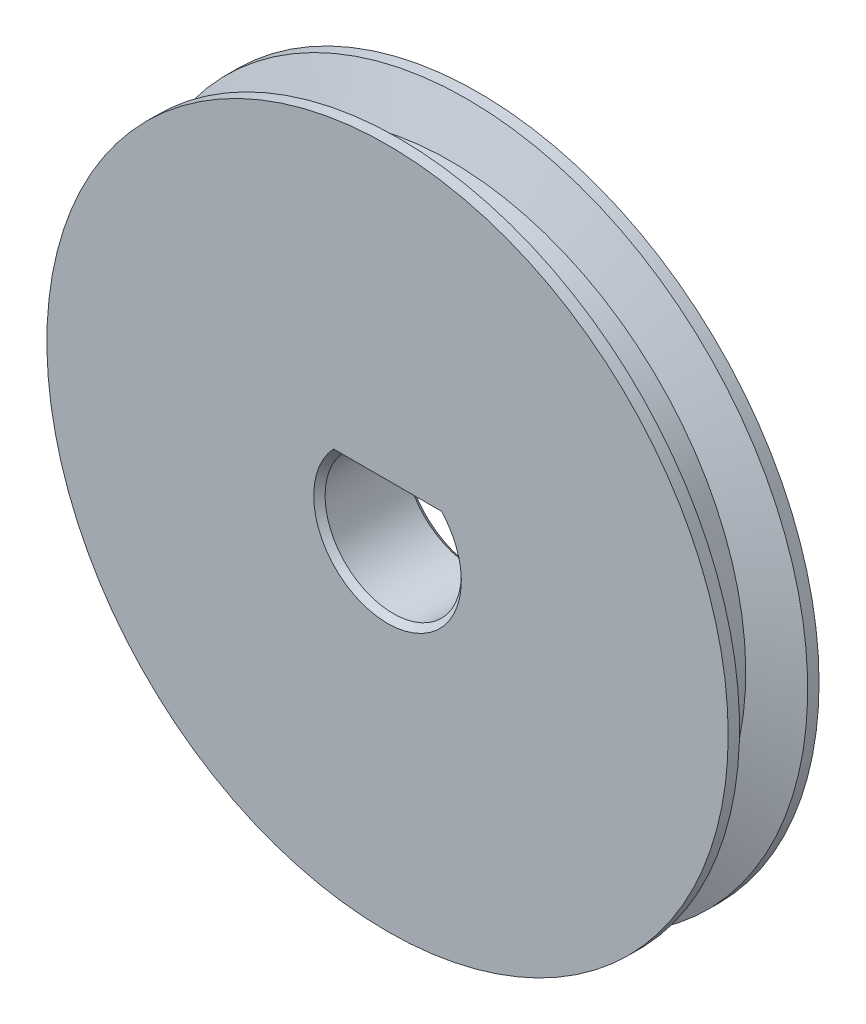
SolidWorks part; units mm, degrees
material "6061-T6 (SS)"
ref_plane "Front Plane" through (0, 0, 0) normal (0, 0, 1) x (1, 0, 0)
ref_plane "Top Plane" through (0, 0, 0) normal (0, 1, 0) x (1, 0, 0)
ref_plane "Right Plane" through (0, 0, 0) normal (1, 0, 0) x (0, 0, -1)
sketch "Sketch1" plane through (0, 0, 0) normal (0, 0, 1) x (1, 0, 0)
  circle A0 centre (0, 0) radius 47.625
  circle A1 centre (0, 0) radius 9.525
  dimension "D1" = 95.25
  dimension "D2" = 19.05
extrude "Extrude1" add sketch "Sketch1" along normal mid plane 12.7
sketch "Sketch2" plane through (0, 0, 0) normal (1, 0, 0) x (0, 0, -1)
  line L0 (-4.7625, 47.625) -> (4.7625, 47.625)
  line L2 (4.7625, 47.625) -> (2.4513, 41.275)
  line L3 (2.4513, 41.275) -> (-2.4513, 41.275)
  line L4 (-2.4513, 41.275) -> (-4.7625, 47.625)
  line L5 (-6.35, 0) -> (6.35, 0) construction
  line L6 (-6.35, 47.625) -> (-6.35, -47.625) construction
  line L7 (6.35, -47.625) -> (6.35, 47.625) construction
  point P2 (0, 47.625)
  point P5 (0, 41.275)
  dimension "D1" = 47.625
  dimension "D2" = 6.35
  dimension "D3" = 9.525
  dimension "D4" = 40
chamfer "Chamfer1" distance 0.7937 angle 45 2 edges at (9.525, 0, -6.35) (9.525, 0, 6.35)
revolve "Cut-Revolve1" cut sketch "Sketch2" angle 360 about L5
sketch "Sketch3" plane through (0, 0, 6.35) normal (0, 0, 1) x (1, 0, 0)
  line L0 (-7.5582, 7.025) -> (7.5582, 7.025)
  line L1 (0, 0) -> (0, 9.525) construction
  circle A2 centre (0, 0) radius 10.3187 construction
  circle A3 centre (0, 0) radius 9.525 construction
  arc A4 (7.5582, 7.025) -> (-7.5582, 7.025) centre (0, 0) ccw
extrude "Boss-Extrude4" add sketch "Sketch3" against normal through all contours A4 L0
